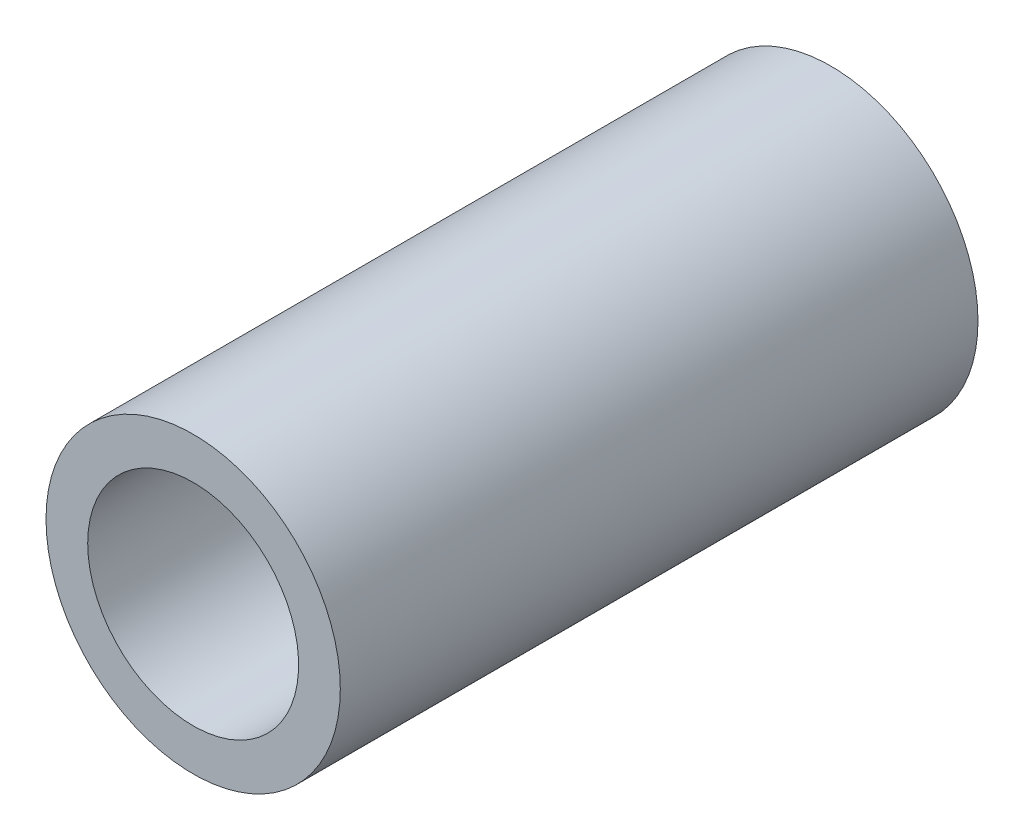
SolidWorks part; units mm, degrees
material "Nylon 101"
ref_plane "Front Plane" through (0, 0, 0) normal (0, 0, 1) x (1, 0, 0)
ref_plane "Top Plane" through (0, 0, 0) normal (0, 1, 0) x (1, 0, 0)
ref_plane "Right Plane" through (0, 0, 0) normal (1, 0, 0) x (0, 0, -1)
sketch "Sketch1" plane through (0, 0, 0) normal (0, 0, 1) x (1, 0, 0)
  circle A0 centre (0, 0) radius 3
  circle A1 centre (0, 0) radius 2.15
  dimension "OD" = 6
  dimension "ID" = 4.3
extrude "Extrude1" add sketch "Sketch1" along normal mid plane 13
sketch "Sketch2" plane through (0, 0, 0) normal (1, 0, 0) x (0, 0, -1)
  line L0 (-6.5, -2.15) -> (6.5, -2.15) construction
  line L3 (6.5, 2.15) -> (-6.5, 2.15) construction
  line L5 (-6.5, -2.15) -> (6.5, -2.15)
  line L6 (6.5, 2.15) -> (-6.5, 2.15)
sketch "Sketch4" plane through (0, 0, 6.5) normal (0, 0, 1) x (1, 0, 0)
  line L0 (0, 0) -> (-1.5203, 1.5203)
  line L1 (0, -3.3) -> (0, 3.3) construction
  circle A0 centre (0, 0) radius 2.15 construction
  dimension "D1" = 45
